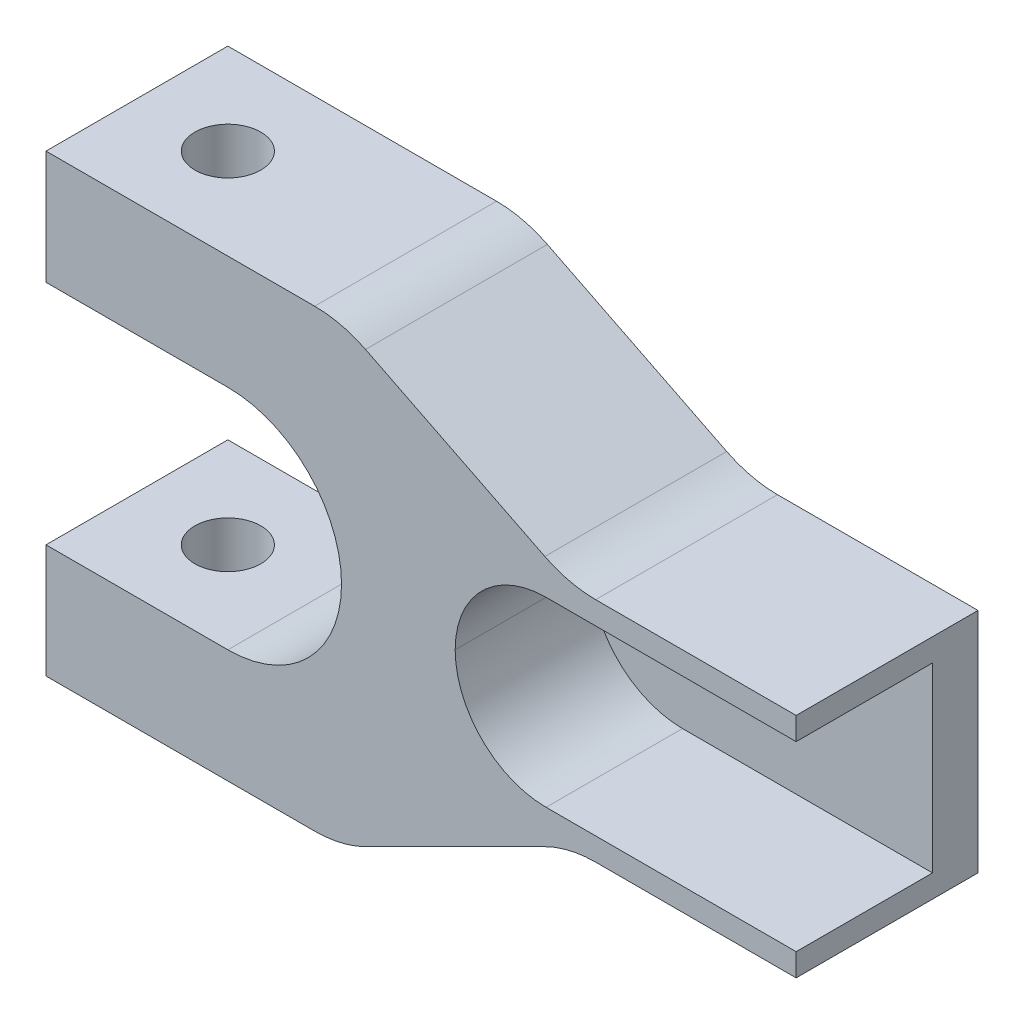
SolidWorks part; units mm, degrees
ref_plane "Face" through (0, 0, 0) normal (0, 0, 1) x (1, 0, 0)
ref_plane "Dessus" through (0, 0, 0) normal (0, 1, 0) x (1, 0, 0)
ref_plane "Droite" through (0, 0, 0) normal (1, 0, 0) x (0, 0, -1)
sketch "Sketch1" plane through (0, 0, 0) normal (0, 0, 1) x (1, 0, 0)
  line L1 (15, 5) -> (15, -5)
  line L4 (5, 5) -> (-5, 10)
  line L5 (-5, 10) -> (-18, 10)
  line L7 (5, -5) -> (-5, -10)
  line L8 (-5, -10) -> (-18, -10)
  line L11 (5, -5) -> (15, -5)
  line L12 (15, 5) -> (5, 5)
  line L14 (-18, -10) -> (-18, -5)
  line L15 (-18, -5) -> (-5, -5)
  line L16 (-5, -5) -> (-5, 5)
  line L17 (-5, 5) -> (-18, 5)
  line L18 (-18, 5) -> (-18, 10)
  dimension "D1" = 10
  dimension "D2" = 10
  dimension "D3" = 10
  dimension "D4" = 15
  dimension "D5" = 10
  dimension "D6" = 20
  dimension "D7" = 5
  dimension "D8" = 10
  dimension "D9" = 5
  dimension "D10" = 13
  dimension "D11" = 5
extrude "Boss-Extrude1" add sketch "Sketch1" against normal mid plane 8
sketch "Sketch3" plane through (15, 0, 0) normal (1, 0, 0) x (0, 0, -1)
  line L0 (-4, -5) -> (-4, 5) construction
  line L1 (-4, 4) -> (2, 4)
  line L2 (-4, 4) -> (-4, -4)
  line L3 (-4, -4) -> (2, -4)
  line L4 (2, 4) -> (2, -4)
  line L6 (4, -5) -> (-4, -5) construction
  dimension "D1" = 6
  dimension "D2" = 8
  dimension "D3" = 1
extrude "Cut-Extrude1" cut sketch "Sketch3" against normal blind 15
fillet "Fillet1" radius 4 2 edges at (0, -4, 1) (0, 4, 1)
sketch "Sketch4" plane through (0, 0, -4) normal (0, 0, -1) x (-1, 0, 0)
  line L0 (-15, -5) -> (-15, 5) construction
  line L2 (-15, 5) -> (-5, 5) construction
  circle A0 centre (-4, 0) radius 1.25
  circle A1 centre (-8, 0) radius 1.25
  point P4 (0, 0)
  dimension "D1" = 2.5
  dimension "D2" = 11
  dimension "D4" = 5
  dimension "D3" = 2
extrude "Cut-Extrude2" cut sketch "Sketch4" against normal through all
fillet "Fillet2" radius 5 2 edges at (-5, 5, 0) (-5, -5, 0)
fillet "Fillet3" radius 5 4 edges at (-5, 10, 0) (5, 5, 0) (-5, -10, 0) (5, -5, 0)
sketch "Sketch6" plane through (0, 10, 0) normal (0, 1, 0) x (1, 0, 0)
  line L0 (-6.1803, -4) -> (-18, -4) construction
  line L1 (-18, 4) -> (-18, -4) construction
  circle A0 centre (-14, 0) radius 1.45
  dimension "D1" = 2.9
  dimension "D2" = 4
  dimension "D3" = 4
extrude "Cut-Extrude3" cut sketch "Sketch6" against normal through all
